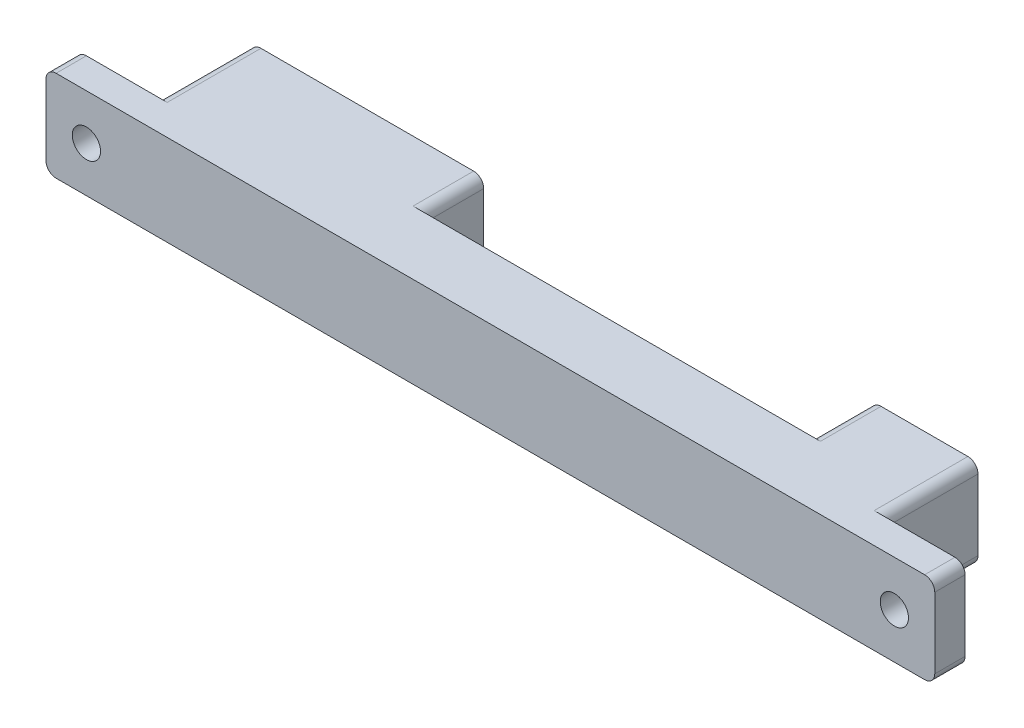
SolidWorks part; units mm, degrees
ref_plane "Front Plane" through (0, 0, 0) normal (0, 0, 1) x (1, 0, 0)
ref_plane "Top Plane" through (0, 0, 0) normal (0, 1, 0) x (1, 0, 0)
ref_plane "Right Plane" through (0, 0, 0) normal (1, 0, 0) x (0, 0, -1)
sketch "Sketch1" plane through (0, 0, 0) normal (0, 0, 1) x (1, 0, 0)
  line L1 (-36, 28.4) -> (36, 28.4)
  line L2 (-36, 28.4) -> (-36, 19.4)
  line L3 (-36, 19.4) -> (36, 19.4)
  line L4 (36, 28.4) -> (36, 19.4)
  line L12 (-12.94, 20.4) -> (-12.94, 27.4)
  line L13 (-12.94, 19.4) -> (-12.94, 28.4)
  line L14 (35, 28.4) -> (35, 7) construction
  line L15 (25.4, 20.4) -> (25.4, 27.4)
  line L16 (25.4, 19.4) -> (25.4, 28.4)
  line L17 (-35, 28.4) -> (-35, 7) construction
  line L19 (-35, 28.4) -> (35, 28.4) construction
  circle A0 centre (32, 23.9) radius 1.4 construction
  circle A1 centre (32, 23.9) radius 1.4 construction
  circle A2 centre (-32, 23.9) radius 1.4 construction
  circle A3 centre (-32, 23.9) radius 1.4 construction
  circle A4 centre (-32, 23.9) radius 1.8
  circle A5 centre (32, 23.9) radius 1.8
  dimension "D6" = 3.6
  dimension "D1" = 9
  dimension "D4" = 1
  dimension "D5" = 1
  dimension "D2" = 1
  dimension "D3" = 1
extrude "Boss-Extrude1" add sketch "Sketch1" along normal up to surface (12.281 mm away) contours A5 | L16 L3 L4 L1 A5 | L3 L13 L1 L2 A4 | A4 | L3 L16 L1 L13 region at (-24.0816, 23.9, 0) region at (6.23, 23.9, 0) region at (30.7, 28.2609, 0) region at (-32, 23.9, 0) region at (32, 23.9, 0)
extrude "Cut-Extrude1" cut sketch "Sketch1<3>" along normal blind 6 contours L3 L16 L1 L13 region at (6.23, 23.9, 0)
sketch "Sketch1<3>" plane through (0, 0, 0) normal (0, 0, 1) x (1, 0, 0) same geometry as "Sketch1"
extrude "Cut-Extrude2" cut sketch "Sketch1<4>" along normal blind 4.5 contours A4 | A5 region at (-32, 23.9, 0) region at (32, 23.9, 0)
sketch "Sketch1<4>" plane through (0, 0, 0) normal (0, 0, 1) x (1, 0, 0) same geometry as "Sketch1"
sketch "Sketch2" plane through (0, 0, 12.281) normal (0, 0, 1) x (1, 0, 0)
  line L0 (36, 19.4) -> (36, 28.4)
  line L1 (36, 19.4) -> (44, 19.4)
  line L2 (36, 28.4) -> (44, 28.4)
  line L3 (44, 19.4) -> (44, 28.4)
  line L4 (-36, 19.4) -> (-36, 28.4)
  line L5 (-36, 19.4) -> (-44, 19.4)
  line L6 (-36, 28.4) -> (-44, 28.4)
  line L7 (-44, 19.4) -> (-44, 28.4)
  line L8 (-44, 19.4) -> (-36, 28.4) construction
  line L9 (36, 19.4) -> (44, 28.4) construction
  circle A0 centre (-40, 23.9) radius 1.4
  circle A1 centre (40, 23.9) radius 1.4
  line M9 (-36, 28.4) -> (-36, 19.4)
  line M11 (36, 19.4) -> (36, 28.4)
  dimension "D2" = 2.8
  dimension "D1" = 8
extrude "Boss-Extrude2" add sketch "Sketch2" against normal blind 3 contours L7 L5 L6 A0 M9 | L1 L3 L2 A1 M11 region at (36.1204, 23.9, 12.281) region at (-40, 19.5204, 12.281)
fillet "Fillet1" radius 1 12 edges at (-12.94, 28.4, 3) (-12.94, 19.4, 3) (25.4, 28.4, 3) (25.4, 19.4, 3) (36, 28.4, 4.6405) (36, 19.4, 4.6405) (44, 19.4, 10.781) (44, 28.4, 10.781) (-36, 19.4, 4.6405) (-36, 28.4, 4.6405) (-44, 28.4, 10.781) (-44, 19.4, 10.781)
chamfer "Chamfer1" distance 0.5 angle 45 2 edges at (33.8, 23.9, 0) (-30.2, 23.9, 0)
